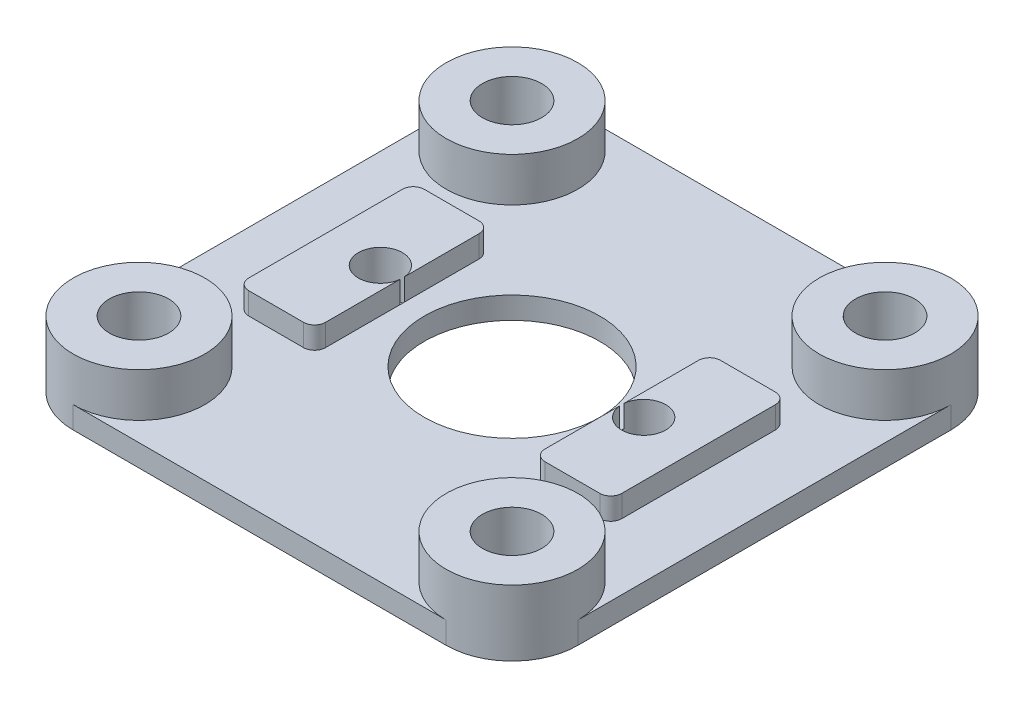
SolidWorks part; units mm, degrees
note: '?' marks a value the reader was unsure of.
material "ABS"
ref_plane "前视基准面" through (0, 0, 0) normal (0, 0, 1) x (1, 0, 0)
ref_plane "上视基准面" through (0, 0, 0) normal (0, 1, 0) x (1, 0, 0)
ref_plane "右视基准面" through (0, 0, 0) normal (1, 0, 0) x (0, 0, -1)
sketch "草图1" plane through (0, 0, 0) normal (0, 1, 0) x (1, 0, 0)
  line L1 (-11.5, -11.5) -> (11.5, -11.5)
  line L2 (-11.5, -11.5) -> (-11.5, 11.5)
  line L3 (-11.5, 11.5) -> (11.5, 11.5)
  line L4 (11.5, -11.5) -> (11.5, 11.5)
  line L5 (-11.5, -11.5) -> (11.5, 11.5) construction
  line L6 (-11.5, 11.5) -> (11.5, -11.5) construction
  point P0 (0, 0)
  dimension "D1" = 23
  dimension "D2" = 23
extrude "凸台-拉伸1" add sketch "草图1" along normal blind 2
sketch "草图2" plane through (0, 2, 0) normal (0, 1, 0) x (1, 0, 0)
  line L1 (-8.5, 8.5) -> (8.5, 8.5)
  line L2 (-8.5, 8.5) -> (-8.5, -8.5)
  line L3 (-8.5, -8.5) -> (8.5, -8.5)
  line L4 (8.5, 8.5) -> (8.5, -8.5)
  line L5 (-8.5, 8.5) -> (8.5, -8.5) construction
  line L6 (-8.5, -8.5) -> (8.5, 8.5) construction
  circle A0 centre (8.5, -8.5) radius 1.35
  point P0 (0, 0)
  dimension "D2" = 2.7
  dimension "D1" = 17
  dimension "16" = 17
extrude "切除-拉伸1" cut sketch "草图2" against normal blind 2 contours L3 A0 L4 | L4 A0 L3
ref_axis "基准轴1" through (0, 0, 0) along (0, 1, 0)?
pattern_circular "阵列(圆周)1" count 4 over 360 about axis through (0, 0, 0) along (0, 1, 0) of "切除-拉伸1"
fillet "圆角1" radius 3 4 edges at (-11.5, 1, 11.5) (11.5, 1, 11.5) (11.5, 1, -11.5) (-11.5, 1, -11.5)
sketch "草图3" plane through (0, 2, 0) normal (0, 1, 0) x (1, 0, 0)
  circle A0 centre (0, 0) radius 4
  dimension "D1" = 8
extrude "切除-拉伸2" cut sketch "草图3" against normal blind 2
sketch "草图4" plane through (0, 2, 0) normal (0, 1, 0) x (1, 0, 0)
  line L0 (-6.75, 0) -> (6.75, 0)
  line L1 (-5, -4) -> (-5, 4)
  line L2 (5, 4) -> (8.5, 4)
  line L3 (5, 4) -> (5, -4)
  line L4 (5, -4) -> (8.5, -4)
  line L5 (8.5, 4) -> (8.5, -4)
  line L6 (5, 4) -> (8.5, -4) construction
  line L7 (5, -4) -> (8.5, 4) construction
  line L8 (-5, -4) -> (-8.5, -4)
  line L9 (-8.5, -4) -> (-8.5, 4)
  line L10 (-5, 4) -> (-8.5, 4)
  line L15 (-8.5, -11.5) -> (8.5, -11.5)
  line L16 (11.5, -8.5) -> (11.5, 8.5)
  line L17 (8.5, 11.5) -> (-8.5, 11.5)
  line L18 (-11.5, 8.5) -> (-11.5, -8.5)
  line L19 (-8.5, -11.5) -> (8.5, -11.5)
  line L20 (11.5, -8.5) -> (11.5, 8.5)
  line L21 (8.5, 11.5) -> (-8.5, 11.5)
  line L22 (-11.5, 8.5) -> (-11.5, -8.5)
  circle A0 centre (-8.5, -8.5) radius 1.35 construction
  circle A1 centre (8.5, -8.5) radius 1.35 construction
  circle A2 centre (8.5, 8.5) radius 1.35 construction
  circle A3 centre (-8.5, 8.5) radius 1.35 construction
  circle A4 centre (-8.5, -8.5) radius 1.35
  circle A5 centre (8.5, -8.5) radius 1.35
  circle A6 centre (8.5, 8.5) radius 1.35
  circle A7 centre (-8.5, 8.5) radius 1.35
  circle A8 centre (-8.5, 8.5) radius 3
  circle A9 centre (8.5, 8.5) radius 3
  circle A10 centre (8.5, -8.5) radius 3
  circle A11 centre (-8.5, -8.5) radius 3
  arc A16 (8.5, -11.5) -> (11.5, -8.5) centre (8.5, -8.5) ccw
  arc A17 (11.5, 8.5) -> (8.5, 11.5) centre (8.5, 8.5) ccw
  arc A18 (-8.5, 11.5) -> (-11.5, 8.5) centre (-8.5, 8.5) ccw
  arc A19 (-11.5, -8.5) -> (-8.5, -11.5) centre (-8.5, -8.5) ccw
  arc A20 (8.5, -11.5) -> (11.5, -8.5) centre (8.5, -8.5) ccw
  arc A21 (11.5, 8.5) -> (8.5, 11.5) centre (8.5, 8.5) ccw
  arc A22 (-8.5, 11.5) -> (-11.5, 8.5) centre (-8.5, 8.5) ccw
  arc A23 (-11.5, -8.5) -> (-8.5, -11.5) centre (-8.5, -8.5) ccw
  point P4 (0, 0)
  dimension "D6" = 6
  dimension "D7" = 6
  dimension "D8" = 6
  dimension "D9" = 6
  dimension "D1" = 5
  dimension "D2" = 3.5
  dimension "D3" = 8
  dimension "D5" = 0
  dimension "D4" = 2
extrude "切除-拉伸6" cut sketch "草图4" against normal blind 1
fillet "圆角2" radius 0.5 8 edges at (-8.5, 1.5, -4) (-5, 1.5, 4) (-5, 1.5, -4) (8.5, 1.5, 4) (8.5, 1.5, -4) (5, 1.5, -4) (5, 1.5, 4) (-8.5, 1.5, 4)
sketch "草图5" plane through (0, 2, 0) normal (0, 1, 0) x (1, 0, 0)
  line L0 (-6, 0) -> (6, 0)
  circle A0 centre (6, 0) radius 1.005
  point P4 (0, 0)
  dimension "D1" = 12
  dimension "D2" = 2.01
extrude "切除-拉伸7" cut sketch "草图5" against normal blind 2
pattern_circular "阵列(圆周)2" count 2 over 360 about axis through (0, 0, 0) along (0, 1, 0) of "切除-拉伸7"
sketch "草图6" plane through (0, 2, 0) normal (0, 1, 0) x (1, 0, 0)
  circle A0 centre (-8.5, -8.5) radius 3 construction
  circle A1 centre (8.5, -8.5) radius 3 construction
  circle A2 centre (8.5, 8.5) radius 3 construction
  circle A3 centre (-8.5, 8.5) radius 3 construction
  circle A4 centre (-8.5, -8.5) radius 3
  circle A5 centre (8.5, -8.5) radius 3
  circle A6 centre (8.5, 8.5) radius 3
  circle A7 centre (-8.5, 8.5) radius 3
  circle A8 centre (-8.5, 8.5) radius 1.35
  circle A9 centre (8.5, 8.5) radius 1.35
  circle A10 centre (-8.5, -8.5) radius 1.35
  circle A11 centre (8.5, -8.5) radius 1.35
extrude "凸台-拉伸2" add sketch "草图6" along normal blind 1
